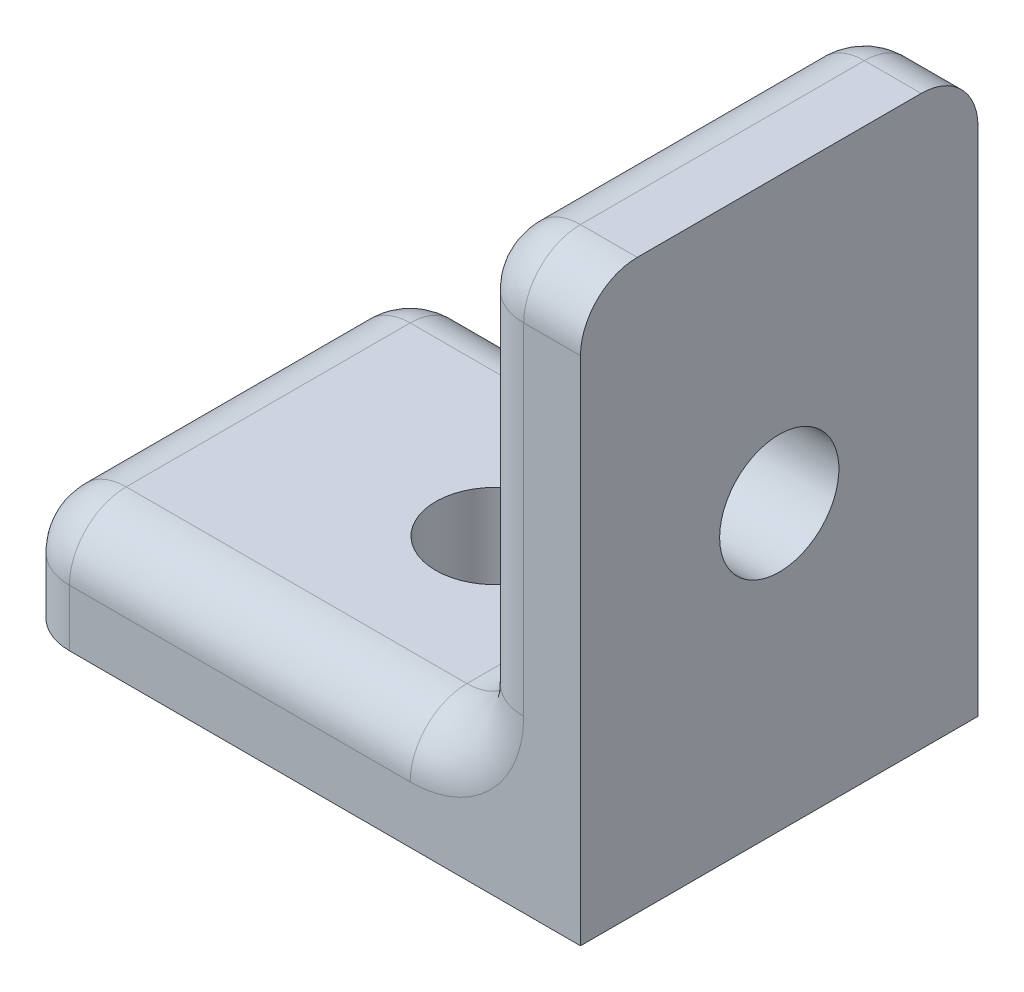
SolidWorks part; units mm, degrees
ref_plane "Front Plane" through (0, 0, 0) normal (0, 0, 1) x (1, 0, 0)
ref_plane "Top Plane" through (0, 0, 0) normal (0, 1, 0) x (1, 0, 0)
ref_plane "Right Plane" through (0, 0, 0) normal (1, 0, 0) x (0, 0, -1)
sketch "Sketch1" plane through (0, 0, 0) normal (0, 1, 0) x (1, 0, 0)
  line L1 (-10, -3.5) -> (0, -3.5)
  line L2 (-10, -3.5) -> (-10, 3.5)
  line L3 (-10, 3.5) -> (0, 3.5)
  line L4 (0, -3.5) -> (0, 3.5)
  point P0 (0, 0)
  point P7 (0, 0)
  dimension "D1" = 10
  dimension "D2" = 7
extrude "Boss-Extrude1" add sketch "Sketch1" along normal blind 2
sketch "Sketch2" plane through (0, 0, 0) normal (1, 0, 0) x (0, 0, -1)
  line L5 (-3.5, 0) -> (3.5, 0)
  line L6 (-3.5, 0) -> (-3.5, 10)
  line L7 (-3.5, 10) -> (3.5, 10)
  line L8 (3.5, 0) -> (3.5, 10)
  dimension "D1" = 10
extrude "Boss-Extrude2" add sketch "Sketch2" against normal blind 2
sketch "Sketch3" plane through (0, 2, 0) normal (0, 1, 0) x (1, 0, 0)
  line L0 (-5, 0) -> (0, 0) construction
  circle A1 centre (-5, 0) radius 1.05
  dimension "D1" = 5
  dimension "D2" = 2.1
extrude "Cut-Extrude1" cut sketch "Sketch3" against normal through all
sketch "Sketch4" plane through (-2, 0, 0) normal (-1, 0, 0) x (0, 0, 1)
  line L0 (0, 5) -> (0, 0) construction
  circle A1 centre (0, 5) radius 1.05
  dimension "D1" = 2.1
  dimension "D2" = 5
extrude "Cut-Extrude2" cut sketch "Sketch4" against normal through all
fillet "Fillet1" radius 1 11 edges at (-2, 2, 0) (-6, 2, 3.5) (-2, 6, 3.5) (-2, 10, 0) (-6, 2, -3.5) (-2, 6, -3.5) (-10, 1, -3.5) (-10, 1, 3.5) (-1, 10, 3.5) (-1, 10, -3.5) (-10, 2, 0)
ref_axis "Axis3" through (0, 5, 0) along (-1, 0, 0)
ref_axis "Axis4" through (-5, 0, 0) along (0, 1, 0)
equation "\"D1@Sketch2\"=\"D1@Sketch1\""
